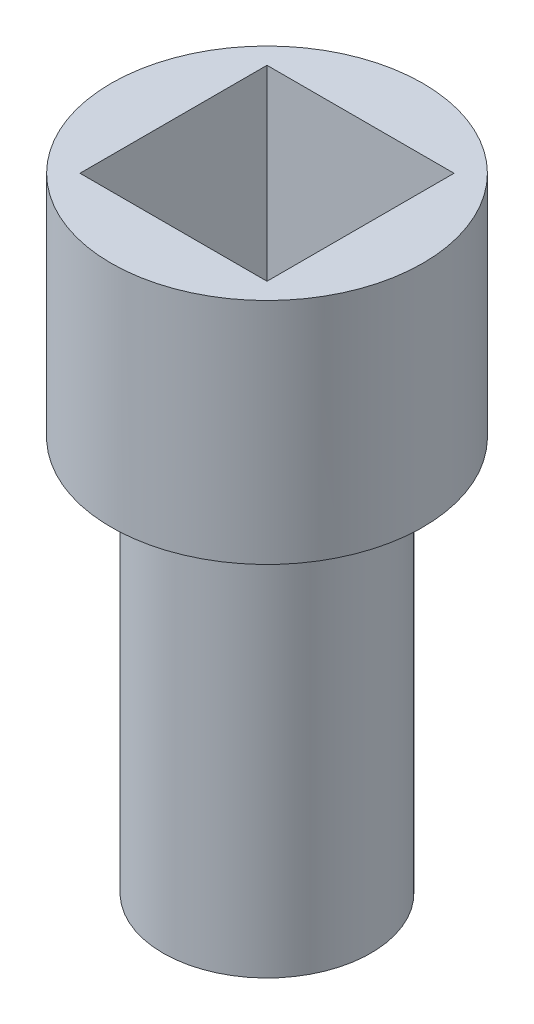
SolidWorks part; units mm, degrees
ref_plane "Front Plane" through (0, 0, 0) normal (0, 0, 1) x (1, 0, 0)
ref_plane "Top Plane" through (0, 0, 0) normal (0, 1, 0) x (1, 0, 0)
ref_plane "Right Plane" through (0, 0, 0) normal (1, 0, 0) x (0, 0, -1)
sketch "Sketch2" plane through (0, 0, 0) normal (0, 1, 0) x (1, 0, 0)
  line L1 (-4.5, -4.5) -> (4.5, -4.5)
  line L2 (-4.5, -4.5) -> (-4.5, 4.5)
  line L3 (-4.5, 4.5) -> (4.5, 4.5)
  line L4 (4.5, -4.5) -> (4.5, 4.5)
  line L5 (-4.5, -4.5) -> (4.5, 4.5) construction
  line L6 (-4.5, 4.5) -> (4.5, -4.5) construction
  circle A0 centre (0, 0) radius 7.5
  circle A1 centre (0, 0) radius 5
  point P0 (0, 0)
  dimension "D2" = 15
  dimension "D3" = 10
  dimension "D1" = 9
extrude "Boss-Extrude1" add sketch "Sketch2" along normal blind 10 contours L3 A1 | L4 A1 | L1 A1 | L2 A1 | A0 A1 L4 L1 L2 L3 region at (0, 0, 4.7009) region at (-4.7009, 0, 0) region at (4.7009, 0, 0) region at (0, 0, -4.7009) region at (-7.2879, 0, 0)
extrude "Boss-Extrude2" add sketch "Sketch2<4>" against normal blind 20 contours A1
sketch "Sketch2<4>" plane through (0, 0, 0) normal (0, 1, 0) x (1, 0, 0) same geometry as "Sketch2"
sketch "Sketch3" plane through (0, -20, 0) normal (0, -1, 0) x (1, 0, 0)
  circle A0 centre (0, 0) radius 2
  dimension "D1" = 4
extrude "Cut-Extrude1" cut sketch "Sketch3" against normal blind 8.5
sketch "Sketch4" plane through (0, 0, 0) normal (0, -1, 0) x (1, 0, 0)
  circle A0 centre (0, 0) radius 7.5
  circle A1 centre (0, 0) radius 7.5 construction
extrude "Boss-Extrude3" add sketch "Sketch4" along normal blind 1
